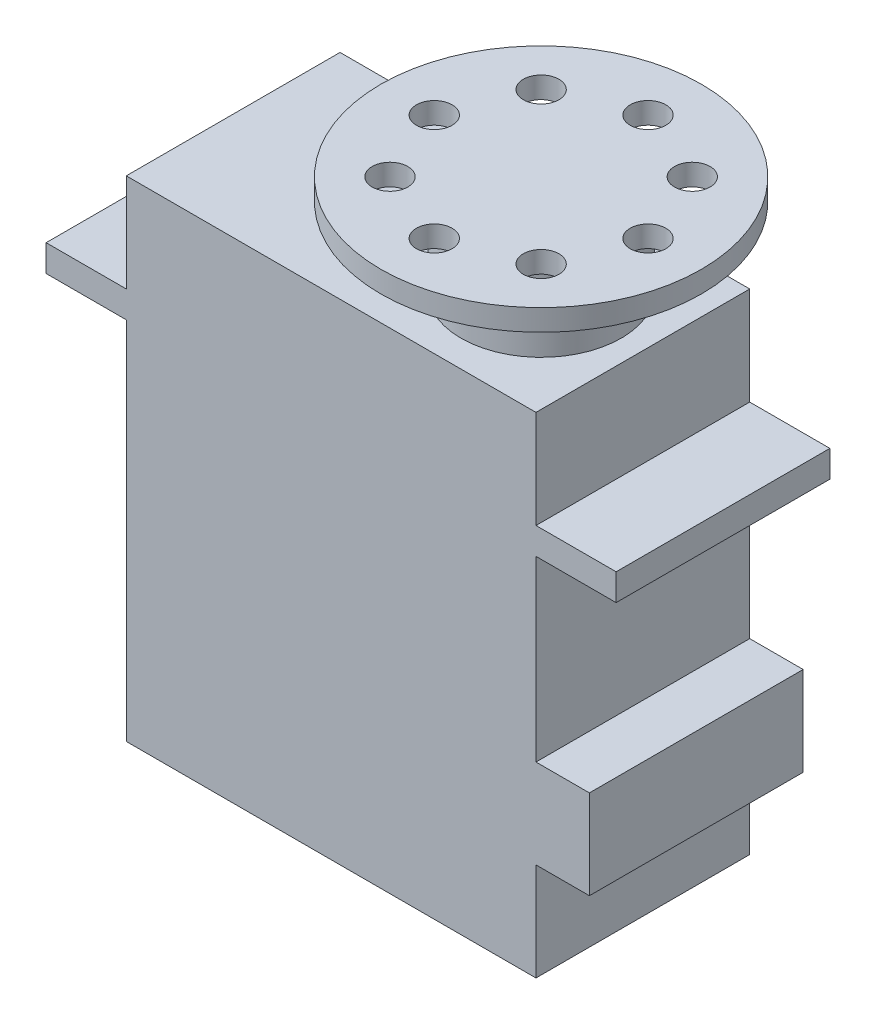
SolidWorks part; units mm, degrees
ref_plane "Front Plane" through (0, 0, 0) normal (0, 0, 1) x (1, 0, 0)
ref_plane "Top Plane" through (0, 0, 0) normal (0, 1, 0) x (1, 0, 0)
ref_plane "Right Plane" through (0, 0, 0) normal (1, 0, 0) x (0, 0, -1)
sketch "Sketch1" plane through (0, 0, 0) normal (0, 0, 1) x (1, 0, 0)
  line L0 (0, 13.75) -> (0, -13.75) construction
  line L1 (-11.5, 0) -> (11.5, 0) construction
  line L3 (11.5, 13.75) -> (-11.5, 13.75)
  line L4 (11.5, 13.75) -> (11.5, -13.75)
  line L5 (11.5, -13.75) -> (-11.5, -13.75)
  line L6 (-11.5, 13.75) -> (-11.5, -13.75)
  dimension "D1" = 27.5
  dimension "D2" = 23
extrude "Boss-Extrude1" add sketch "Sketch1" along normal blind 6 and the other way blind 6
sketch "Sketch4" plane through (0, 13.75, 0) normal (0, 1, 0) x (1, 0, 0)
  line L0 (-11.5, 0) -> (11.5, 0) construction
  line L1 (5.79, 6) -> (5.79, -6) construction
  line L2 (11.5, 6) -> (11.5, -6) construction
  circle A0 centre (5.79, 0) radius 4.5
  dimension "D2" = 9
  dimension "D1" = 5.71
extrude "Boss-Extrude2" add sketch "Sketch4" along normal blind 4.4
sketch "Sketch5" plane through (0, 18.15, 0) normal (0, 1, 0) x (1, 0, 0)
  circle A0 centre (5.79, 0) radius 9
  dimension "D2" = 18
extrude "Boss-Extrude3" add sketch "Sketch5" along normal blind 1.2
sketch "Sketch6" plane through (0, 19.35, 0) normal (0, 1, 0) x (1, 0, 0)
  line L0 (5.79, 9) -> (5.79, -9) construction
  line L1 (-3.21, 0) -> (14.79, 0) construction
  circle A0 centre (5.79, 0) radius 6 construction
  circle A1 centre (5.79, 6) radius 1
  circle A2 centre (10.0326, 4.2426) radius 1
  circle A3 centre (11.79, 0) radius 1
  circle A4 centre (10.0326, -4.2426) radius 1
  circle A5 centre (5.79, -6) radius 1
  circle A6 centre (1.5474, -4.2426) radius 1
  circle A7 centre (-0.21, 0) radius 1
  circle A8 centre (1.5474, 4.2426) radius 1
  dimension "D1" = 12
  dimension "D2" = 2
  dimension "D3" = 8
extrude "Cut-Extrude1" cut sketch "Sketch6" against normal up to surface (1.2 mm away) up to face at (5.79, 18.15, 4.5)
sketch "Sketch7" plane through (-11.5, 0, 0) normal (-1, 0, 0) x (0, 0, 1)
  line L1 (-6, 6.75) -> (6, 6.75)
  line L2 (-6, -13.75) -> (6, -13.75) construction
  line L3 (6, 8.25) -> (-6, 8.25)
  line L4 (-6, 8.25) -> (-6, 6.75)
  line L5 (6, 8.25) -> (6, 6.75)
  dimension "D1" = 20.5
  dimension "D2" = 22
extrude "Boss-Extrude4" add sketch "Sketch7" along normal blind 4.5
mirror "Mirror1" about plane through (0, 0, 0) normal (1, 0, 0) of "Boss-Extrude4"
sketch "Sketch8" plane through (11.5, 0, 0) normal (1, 0, 0) x (0, 0, -1)
  line L0 (-6, -3.25) -> (6, -3.25)
  line L1 (6, -13.75) -> (-6, -13.75) construction
  line L2 (-6, -8.25) -> (6, -8.25)
  line L3 (-6, -8.25) -> (-6, -3.25)
  line L4 (6, -8.25) -> (6, -3.25)
  dimension "D1" = 10.5
  dimension "D2" = 5
extrude "Boss-Extrude5" add sketch "Sketch8" along normal blind 3
